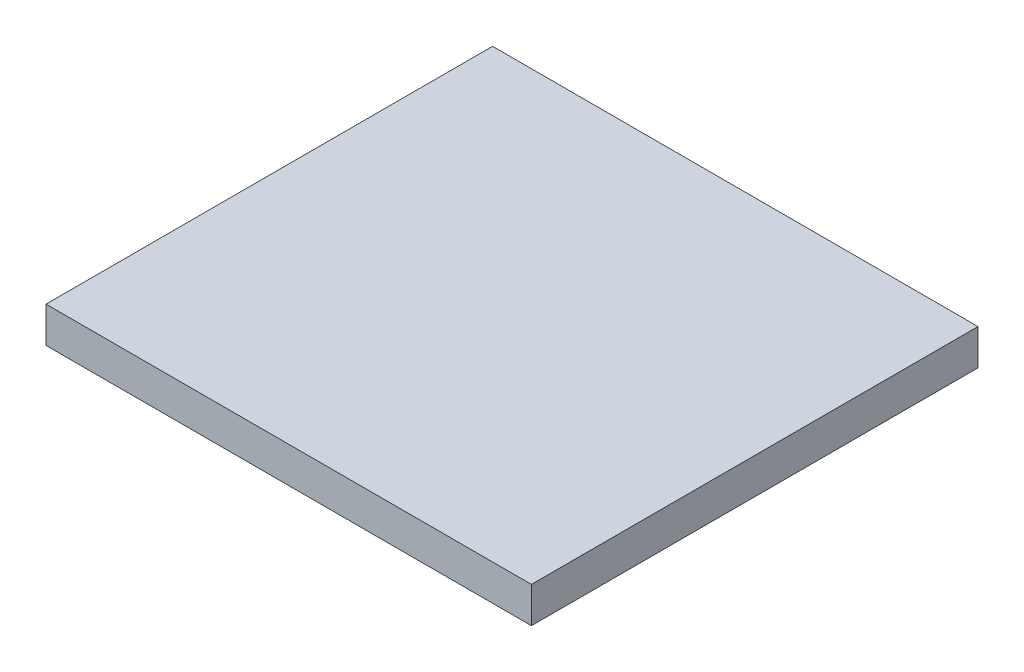
SolidWorks part; units mm, degrees
ref_plane "Front" through (0, 0, 0) normal (0, 0, 1) x (1, 0, 0)
ref_plane "Top" through (0, 0, 0) normal (0, 1, 0) x (1, 0, 0)
ref_plane "Right" through (0, 0, 0) normal (1, 0, 0) x (0, 0, -1)
sketch "Sketch1" plane through (0, 0, 0) normal (0, 1, 0) x (1, 0, 0)
  line L1 (-62.5, -57.5) -> (62.5, -57.5)
  line L2 (-62.5, -57.5) -> (-62.5, 57.5)
  line L3 (-62.5, 57.5) -> (62.5, 57.5)
  line L4 (62.5, -57.5) -> (62.5, 57.5)
  line L5 (-62.5, -57.5) -> (62.5, 57.5) construction
  line L6 (-62.5, 57.5) -> (62.5, -57.5) construction
  point P0 (0, 0)
  dimension "D1" = 125
  dimension "D2" = 115
extrude "Test_Base_Postion" add sketch "Sketch1" along normal blind 9.215
sketch "Thumb_Position" plane through (0, 9.215, 0) normal (0, 1, 0) x (1, 0, 0)
  line L0 (62.5, -57.5) -> (62.5, 57.5) construction
  line L1 (49, -12) -> (17, -12)
  line L2 (49, -12) -> (49, 43)
  line L3 (49, 43) -> (17, 43)
  line L4 (17, -12) -> (17, 43)
  line L5 (33, 43) -> (33, -12) construction
  line L6 (51, -12) -> (15, -12)
  line L7 (51, -12) -> (51, 12)
  line L8 (51, 12) -> (15, 12)
  line L9 (15, -12) -> (15, 12)
  line L10 (33, 12) -> (33, -12) construction
  line L12 (51, 0) -> (15, 0) construction
  circle A1 centre (42, 0) radius 9
  circle A2 centre (42, 0) radius 17.75 construction
  dimension "D6" = 18
  dimension "D7" = 20.5
  dimension "D5" = 35.5
  dimension "D1" = 55
  dimension "D2" = 32
  dimension "D3" = 36
  dimension "D4" = 24
sketch "Finger_Gears_Position" plane through (0, 0, 0) normal (0, -1, 0) x (1, 0, 0)
  line L0 (-30, 35) -> (-30, 52.5) construction
  line L1 (-30, 35) -> (-47.5, 35) construction
  line L2 (-30, -35) -> (-30, -52.5) construction
  line L3 (-30, -35) -> (-47.5, -35) construction
  line L4 (-62.5, -57.5) -> (-62.5, 57.5) construction
  line L5 (-62.5, 57.5) -> (62.5, 57.5) construction
  line L8 (62.5, -57.5) -> (-62.5, -57.5) construction
  line L9 (-62.5, 0) -> (62.5, 0) construction
  line L10 (62.5, 57.5) -> (62.5, -57.5) construction
  line L13 (-30, -35) -> (-43, -35) construction
  line L15 (-43, -51) -> (12, -51) construction
  line L16 (-43, -51) -> (-43, -19) construction
  line L17 (-43, -19) -> (12, -19) construction
  line L18 (12, -51) -> (12, -19) construction
  line L20 (-30, 35) -> (-43, 35) construction
  line L21 (12, -35) -> (-23, -35) construction
  line L22 (-43, 19) -> (12, 19) construction
  line L23 (-43, 19) -> (-43, 51) construction
  line L24 (-43, 51) -> (12, 51) construction
  line L25 (12, 19) -> (12, 51) construction
  line L26 (12, 35) -> (-23, 35) construction
  line L27 (-23, -35) -> (-23, 35) construction
  circle A0 centre (-30, 35) radius 17.5 construction
  circle A1 centre (-30, -35) radius 17.5 construction
  dimension "D1" = 35
  dimension "D2" = 15
  dimension "D3" = 5
  dimension "D4" = 5
  dimension "D5" = 13
  dimension "D6" = 55
  dimension "D7" = 32
  dimension "D8" = 13
  dimension "D9" = 55
  dimension "D10" = 32
  dimension "D11" = 35
  dimension "D12" = 35
sketch "Fingers_Position" plane through (0, 9.215, 0) normal (0, 1, 0) x (1, 0, 0)
  line L0 (12, 35) -> (-23, 35) construction
  line L1 (12, 19) -> (-43, 19)
  line L2 (12, 19) -> (12, 51)
  line L3 (12, 51) -> (-43, 51)
  line L4 (-43, 19) -> (-43, 51)
  line L5 (12, -51) -> (-43, -51)
  line L6 (12, -51) -> (12, -19)
  line L7 (12, -19) -> (-43, -19)
  line L8 (-43, -51) -> (-43, -19)
  line L9 (-23, 35) -> (-23, -35) construction
  line L10 (-23, -35) -> (12, -35) construction
sketch "Thumb_Knuckle_Mount_Position" plane through (0, 0, 0) normal (0, -1, 0) x (1, 0, 0)
  circle A0 centre (42, 0) radius 17.75
  dimension "D1" = 35.5
